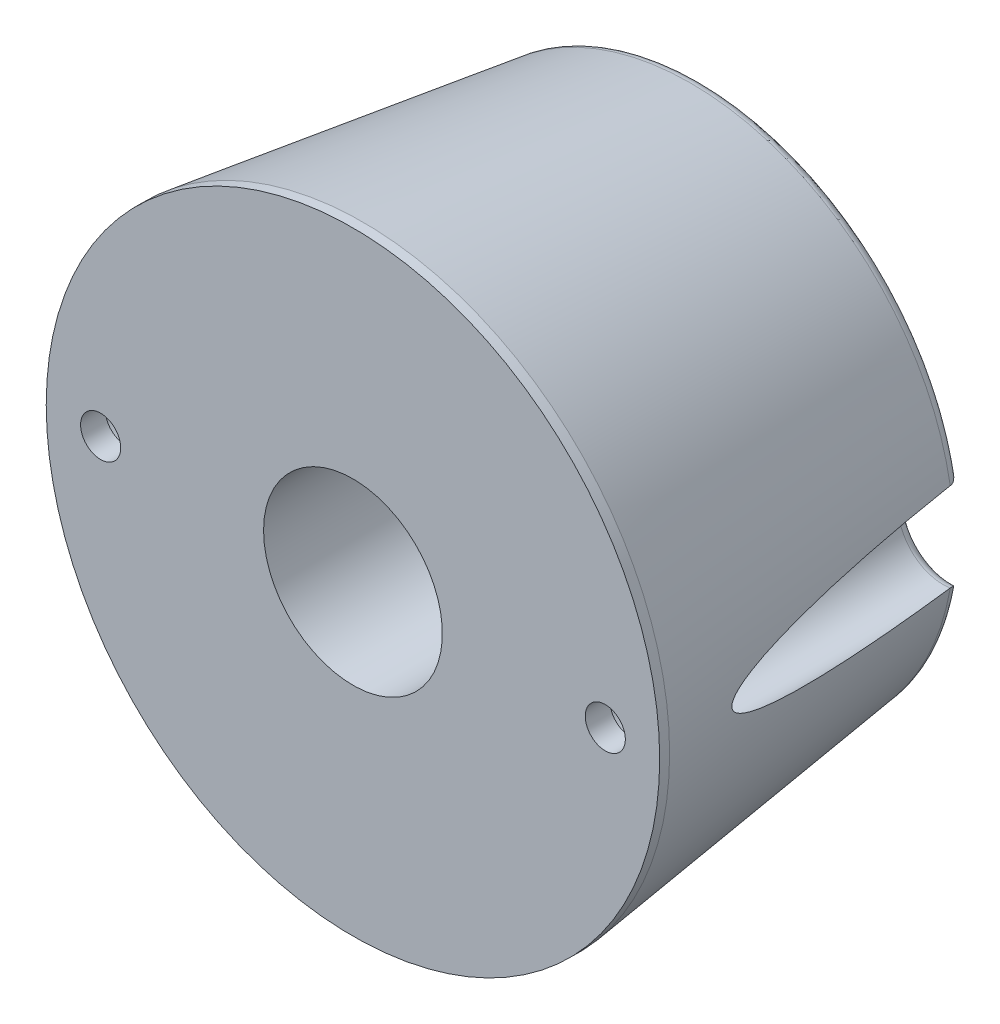
SolidWorks part; units mm, degrees
ref_plane "Front Plane" through (0, 0, 0) normal (0, 0, 1) x (1, 0, 0)
ref_plane "Top Plane" through (0, 0, 0) normal (0, 1, 0) x (1, 0, 0)
ref_plane "Right Plane" through (0, 0, 0) normal (1, 0, 0) x (0, 0, -1)
sketch "Sketch1" plane through (0, 0, 0) normal (0, 0, 1) x (1, 0, 0)
  circle A0 centre (0, 0) radius 26.5
  circle A1 centre (-15.35, -15.5) radius 1.5
  circle A2 centre (15.35, -15.5) radius 1.5
  circle A3 centre (15.35, 15.5) radius 1.5
  circle A4 centre (-15.35, 15.5) radius 1.5
  dimension "D6" = 53
  dimension "D8" = 3
  dimension "D1" = 30.7
  dimension "D2" = 31
  dimension "D3" = 21.8145
  dimension "D4" = 31
  dimension "D5" = 30.7
  dimension "D7" = 15.35
ref_plane "Plane1" through (0, 0, 33) normal (0, 0, 1) x (1, 0, 0)
sketch "Sketch2" plane through (0, 0, 33) normal (0, 0, 1) x (1, 0, 0)
  arc A0 (27.4193, 0) -> (23.3807, 0) centre (25.4, 0) ccw
  arc A1 (23.3807, 0) -> (27.4193, 0) centre (25.4, 0) ccw
  arc A2 (-23.3807, 0) -> (-27.4193, 0) centre (-25.4, 0) ccw
  arc A3 (-27.4193, 0) -> (-23.3807, 0) centre (-25.4, 0) ccw
  circle A6 centre (0, 0) radius 30.877
  dimension "D1" = 2.0193
  dimension "D2" = 61.754
  dimension "D4" = 25.4
  dimension "D3" = 25.4
extrude "Boss-Extrude1" add sketch "Sketch1" against normal blind 1
extrude "Boss-Extrude2" add sketch "Sketch2" along normal blind 1 separate body
loft "Loft1" add section edge at (26.5, 0, 0) section edge at (30.877, 0, 33)
extrude "Cut-Extrude1" cut sketch "Sketch1<5>" along normal blind 5 contours A3 | A4 | A1 | A2 region at (-15.35, -15.5, 0) region at (15.35, -15.5, 0) region at (15.35, 15.5, 0) region at (-15.35, 15.5, 0)
sketch "Sketch1<5>" plane through (0, 0, 0) normal (0, 0, 1) x (1, 0, 0) same geometry as "Sketch1"
extrude "Cut-Extrude2" cut sketch "Sketch2<6>" against normal through all contours A0 A1 | A2 A3 region at (25.4, 0, 33) region at (-25.4, 0, 33)
sketch "Sketch2<6>" plane through (0, 0, 33) normal (0, 0, 1) x (1, 0, 0) same geometry as "Sketch2"
sketch "Sketch3" plane through (0, 0, -1) normal (0, 0, -1) x (-1, 0, 0)
  line L0 (0, 0) -> (0, 26.5) construction
  arc A0 (-26.4436, 1.7287) -> (-26.4436, -1.7287) centre (-25.4, 0) ccw construction
  arc A1 (-26.4436, -1.7287) -> (-26.4436, 1.7287) centre (-25.4, 0) ccw construction
  arc A2 (-26.4436, 1.7287) -> (-26.4436, -1.7287) centre (-25.4, 0) ccw
  arc A3 (-26.4436, -1.7287) -> (-26.4436, 1.7287) centre (-25.4, 0) ccw
  arc A4 (-27.7355, -3.869) -> (-27.7355, 3.869) centre (-25.4, 0) ccw
  arc A5 (-27.7355, 3.869) -> (-27.7355, -3.869) centre (-25.4, 0) ccw
  arc A6 (26.4436, 1.7287) -> (-26.4436, 1.7287) centre (0, 0) ccw construction
  arc A7 (27.7355, -3.869) -> (27.7355, 3.869) centre (25.4, 0) cw
  arc A8 (27.7355, 3.869) -> (27.7355, -3.869) centre (25.4, 0) cw
  dimension "D1" = 2.5
extrude "Cut-Extrude3" cut sketch "Sketch3" against normal offset from surface (32.5 mm away) 2.5 up to face at (27.4193, 0, 34)
sketch "Sketch4" plane through (0, 0, -1) normal (0, 0, -1) x (-1, 0, 0)
  circle A0 centre (0, 0) radius 9
  dimension "D1" = 18
extrude "Cut-Extrude4" cut sketch "Sketch4" against normal through all
fillet "Fillet1" radius 1 4 edges at (-20.8807, 0, -1) (0, -26.5, -1) (20.8807, 0, -1) (0, 26.5, -1)
sketch "Sketch5" plane through (0, 0, -1) normal (0, 0, -1) x (-1, 0, 0)
  circle A0 centre (0, 0) radius 6.5
  circle A1 centre (0, 0) radius 9
  dimension "D1" = 13
  dimension "D2" = 18
extrude "Boss-Extrude3" add sketch "Sketch5" against normal blind 2 from offset 5 separate body offset against normal yes
